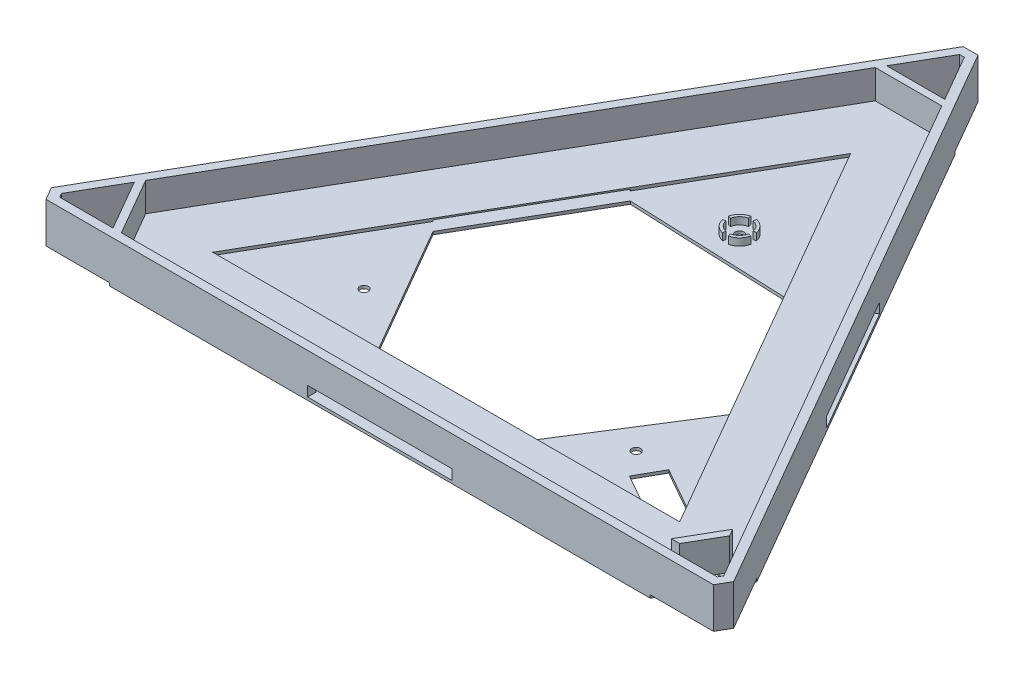
SolidWorks part; units mm, degrees
ref_plane "Front Plane" through (0, 0, 0) normal (0, 0, 1) x (1, 0, 0)
ref_plane "Top Plane" through (0, 0, 0) normal (0, 1, 0) x (1, 0, 0)
ref_plane "Right Plane" through (0, 0, 0) normal (1, 0, 0) x (0, 0, -1)
sketch "Sketch1" plane through (0, 0, 0) normal (0, 1, 0) x (1, 0, 0)
  line L0 (351.2729, 67.6655) -> (468.273, -134.9846)
  line L1 (347.2728, 67.6655) -> (347.2728, 65.1655) construction
  line L2 (409.773, -33.6595) -> (407.6079, -34.9095) construction
  line L3 (468.273, -134.9846) -> (464.2732, -141.9124)
  line L4 (230.2733, -141.9124) -> (464.2732, -141.9124)
  line L5 (230.2733, -141.9124) -> (226.2727, -134.9842)
  line L6 (226.2727, -134.9842) -> (343.2728, 67.6655)
  line L7 (353.4142, 63.9567) -> (351.2491, 62.7067) construction
  line L8 (347.2733, -141.9124) -> (347.2733, -139.4124) construction
  line L9 (231.7167, -139.4124) -> (462.8299, -139.4124)
  line L10 (284.7727, -33.6594) -> (286.9378, -34.9094) construction
  line L11 (344.7161, 65.1655) -> (349.8295, 65.1655)
  line L12 (465.3862, -134.9846) -> (349.8295, 65.1655)
  line L13 (466.2731, -138.4485) -> (464.1081, -137.1985) construction
  line L14 (462.8299, -139.4124) -> (465.3862, -134.9846)
  line L15 (229.1594, -134.9842) -> (344.7161, 65.1655)
  line L16 (229.1594, -134.9842) -> (231.7167, -139.4124)
  line L17 (286.9378, -34.9094) -> (287.3708, -35.1594) construction
  line L18 (230.438, -137.1983) -> (230.871, -136.9483) construction
  line L19 (232.0053, -138.9123) -> (229.7368, -134.9842)
  line L20 (343.2728, 67.6655) -> (351.2729, 67.6655)
  line L21 (345.0048, 64.6655) -> (229.7368, -134.9842)
  line L22 (349.5409, 64.6655) -> (345.0048, 64.6655)
  line L23 (249.0568, -126.4468) -> (246.8918, -127.697) construction
  line L24 (407.6079, -34.9095) -> (407.1749, -35.1595) construction
  line L26 (233.4463, -136.4089) -> (251.9226, -136.4093)
  line L27 (464.8089, -134.9846) -> (462.5412, -138.9123)
  line L28 (462.5412, -138.9123) -> (232.0053, -138.9123)
  line L29 (251.9226, -136.4093) -> (241.8609, -118.9847)
  line L30 (241.8609, -118.9847) -> (232.6236, -134.9842)
  line L31 (232.6236, -134.9842) -> (233.4463, -136.4089)
  line L33 (287.3708, -35.1594) -> (289.5359, -36.4094) construction
  line L34 (254.8093, -136.4089) -> (243.3042, -116.4848)
  line L35 (335.7675, 43.666) -> (243.3042, -116.4848)
  line L36 (358.7782, 43.666) -> (335.7675, 43.666)
  line L38 (289.5359, -36.4094) -> (306.8564, -46.4094) construction
  line L41 (461.939, -134.9846) -> (461.1164, -136.4093)
  line L42 (347.2688, -136.4172) -> (347.2688, -116.4172) construction
  line L43 (442.6021, -136.4093) -> (452.6999, -118.9847)
  line L44 (245.2636, -119.878) -> (249.0568, -126.4468) construction
  line L45 (452.6999, -118.9847) -> (461.939, -134.9846)
  line L48 (461.1164, -136.4093) -> (442.6021, -136.4093)
  line L49 (405.0134, -36.4027) -> (387.6936, -46.404) construction
  line L50 (306.8564, -46.4094) -> (466.2731, -138.4485) construction
  line L51 (357.3348, 46.166) -> (337.2109, 46.166)
  line L52 (337.2109, 46.166) -> (346.4484, 62.1659)
  line L53 (346.4484, 62.1659) -> (348.0966, 62.164)
  line L54 (348.0966, 62.164) -> (357.3348, 46.166)
  line L55 (228.273, -138.4483) -> (387.6936, -46.404) construction
  line L56 (347.2688, -116.4172) -> (347.2728, 43.666) construction
  line L57 (266.4391, -116.428) -> (428.1137, -116.4172)
  line L58 (347.2736, 23.6092) -> (428.1137, -116.4172)
  line L59 (266.4391, -116.428) -> (347.2736, 23.6092)
  line L60 (439.7283, -136.4254) -> (439.7283, -132.9254) construction
  line L61 (451.2487, -116.4715) -> (448.6507, -117.9717) construction
  line L62 (452.6999, -118.9847) -> (358.7782, 43.666)
  line L63 (442.6021, -136.4093) -> (254.8093, -136.4089)
  line L64 (441.749, -132.9254) -> (444.621, -132.9254)
  line L65 (448.6507, -117.9717) -> (450.9647, -121.979) construction
  line L66 (449.5167, -119.4714) -> (450.9647, -121.979)
  line L67 (441.749, -132.9254) -> (449.5167, -119.4714)
  line L68 (450.9647, -121.979) -> (444.621, -132.9254)
  point P13 (407.6079, -34.9095)
  point P20 (464.1081, -137.1985)
  point P23 (347.2733, -139.4124)
  point P25 (347.2732, -141.9124)
  point P27 (347.2728, 65.1655)
  point P31 (286.9378, -34.9094)
  point P37 (287.3708, -35.1594)
  point P39 (230.871, -136.9483)
  point P41 (347.2728, 64.6655)
  point P45 (407.1749, -35.1595)
  point P50 (246.8918, -127.697)
  point P56 (289.5359, -36.4094)
  point P58 (249.0568, -126.4468)
  point P60 (347.2728, 43.666)
  point P62 (345.0048, -136.4089)
  point P64 (445.4885, -126.4485)
  point P71 (447.651, -127.697)
  point P77 (347.2728, 46.166)
  point P84 (347.2688, -116.4172)
  point P87 (387.6936, -46.404)
  point P89 (306.8564, -46.4094)
  point P100 (405.0134, -36.4027)
  dimension "D1" = 2.5
  dimension "D2" = 2.5
  dimension "D3" = 2.5
  dimension "D4" = 2.5
  dimension "D5" = 2.5
  dimension "D6" = 2.5
  dimension "D7" = 0.5
  dimension "D8" = 0.5
  dimension "D9" = 0.5
  dimension "D10" = 2.5
  dimension "D11" = 2.5
  dimension "D12" = 20
  dimension "D13" = 20
  dimension "D14" = 20
  dimension "D15" = 3.5
  dimension "D16" = 3
extrude "Boss-Extrude1" add sketch "Sketch1" along normal blind 1 contours L36 L35 L34 L57 L59 L58 region at (251.4484, 0, 125.0658)
extrude "Boss-Extrude2" add sketch "Sketch1<9>" along normal blind 11 contours L28 L27 L22 L21 L19 L31 L30 L29 L26 L34 L35 L36 L41 L48 L43 L45 L53 L54 L51 L52 | L68 L64 L67 L66 region at (230.7087, 0, 137.042)
sketch "Sketch1<9>" plane through (0, 0, 0) normal (0, 1, 0) x (1, 0, 0) same geometry as "Sketch1"
extrude "Boss-Extrude3" add sketch "Sketch1<10>" along normal blind 5 and the other way blind 3 contours L28 L27 L22 L21 L19 L31 L30 L29 L26 L34 L35 L36 L41 L48 L43 L45 L53 L54 L51 L52 region at (230.7087, 0, 137.042)
sketch "Sketch1<10>" plane through (0, 0, 0) normal (0, 1, 0) x (1, 0, 0) same geometry as "Sketch1"
sketch "Sketch3" plane through (290.5896, 0, -167.772) normal (0.866, 0, -0.5) x (-0.5, 0, -0.866)
  line L1 (-261.593, -6.5) -> (-211.593, -6.5)
  line L2 (-261.593, -6.5) -> (-261.593, 0.5)
  line L3 (-261.593, 0.5) -> (-211.593, 0.5)
  line L4 (-211.593, -6.5) -> (-211.593, 0.5)
  line L5 (-261.593, -6.5) -> (-211.593, 0.5) construction
  line L6 (-261.593, 0.5) -> (-211.593, -6.5) construction
  point P0 (-236.593, -3)
  dimension "D1" = 50
  dimension "D2" = 7
extrude "Cut-Extrude3" cut sketch "Sketch3" against normal blind 25
sketch "Sketch5" plane through (0, 0, 139.4124) normal (0, 0, 1) x (1, 0, 0)
  line L0 (231.7167, -3) -> (462.8299, -3) construction
  line L1 (322.2733, -6.5) -> (372.2733, -6.5)
  line L2 (322.2733, -6.5) -> (322.2733, 0.5)
  line L3 (322.2733, 0.5) -> (372.2733, 0.5)
  line L4 (372.2733, -6.5) -> (372.2733, 0.5)
  line L5 (322.2733, -6.5) -> (372.2733, 0.5) construction
  line L6 (322.2733, 0.5) -> (372.2733, -6.5) construction
  point P0 (347.2733, -3)
  dimension "D1" = 50
  dimension "D2" = 7
extrude "Cut-Extrude4" cut sketch "Sketch5" against normal blind 25
sketch "Sketch6" plane through (230.3194, 0, 132.9752) normal (-0.866, 0, -0.5) x (-0.5, 0, 0.866)
  line L0 (2.3199, -3) -> (-228.7932, -3) construction
  line L1 (-138.2367, -6.5) -> (-88.2367, -6.5)
  line L2 (-138.2367, -6.5) -> (-138.2367, 0.5)
  line L3 (-138.2367, 0.5) -> (-88.2367, 0.5)
  line L4 (-88.2367, -6.5) -> (-88.2367, 0.5)
  line L5 (-138.2367, -6.5) -> (-88.2367, 0.5) construction
  line L6 (-138.2367, 0.5) -> (-88.2367, -6.5) construction
  point P0 (-113.2367, -3)
  dimension "D1" = 50
  dimension "D2" = 7
extrude "Cut-Extrude5" cut sketch "Sketch6" against normal blind 25
sketch "Sketch8" plane through (0, -3, 0) normal (0, -1, 0) x (1, 0, 0)
  line L0 (246.8918, 127.697) -> (257.9651, 146.8734) construction
  line L1 (251.9226, 136.4093) -> (241.8609, 118.9847) construction
  line L2 (447.651, 127.697) -> (454.4275, 116.0035) construction
  line L3 (442.6021, 136.4093) -> (452.6999, 118.9847) construction
  line L4 (465.3862, 134.9846) -> (421.3861, 58.7742) construction
  line L5 (347.2728, -46.166) -> (333.7468, -46.166) construction
  line L6 (357.3348, -46.166) -> (337.2109, -46.166) construction
  line L7 (299.4378, 13.2587) -> (344.7161, -65.1655) construction
  line L8 (246.8918, 127.697) -> (240.1287, 115.9849)
  line L9 (229.1594, 134.9842) -> (274.4378, 56.56) construction
  line L10 (240.1287, 115.9849) -> (333.7468, -46.166)
  line L11 (333.7468, -46.166) -> (360.7989, -46.166)
  line L12 (396.3861, 15.4729) -> (349.8295, -65.1655) construction
  line L13 (360.7989, -46.166) -> (454.4275, 116.0035)
  line L15 (372.2733, 139.4124) -> (462.8299, 139.4124) construction
  line L16 (440.9124, 139.4124) -> (253.6568, 139.4124)
  line L17 (231.7167, 139.4124) -> (322.2733, 139.4124) construction
  line L18 (253.6568, 139.4124) -> (246.8918, 127.697)
  line L19 (322.2733, 116.4243) -> (294.3582, 68.0611)
  line L20 (294.3582, 68.0611) -> (319.3545, 24.7577)
  line L21 (319.3545, 24.7577) -> (376.4737, 26.9694)
  line L22 (376.4737, 26.9694) -> (401.4727, 70.2712)
  line L23 (401.4727, 70.2712) -> (372.2733, 116.4209)
  line L24 (372.2733, 116.4209) -> (322.2733, 116.4243)
  line L25 (386.873, 93.3461) -> (395.3235, 98.6928) construction
  line L30 (308.3157, 92.2427) -> (299.6549, 97.2417) construction
  line L31 (347.9141, 25.8635) -> (348.3013, 15.8635) construction
  line L32 (440.9124, 139.4124) -> (445.2267, 131.9864)
  line L33 (454.4275, 116.0035) -> (450.147, 123.2807)
  line L34 (401.698, 107.3846) -> (445.2267, 131.9864)
  line L35 (450.147, 123.2807) -> (406.6183, 98.6788)
  line L36 (401.698, 107.3846) -> (406.6183, 98.6788)
  circle A0 centre (395.3235, 98.6928) radius 1.5
  circle A1 centre (348.3013, 15.8635) radius 1.5
  circle A2 centre (299.6549, 97.2417) radius 1.5
  dimension "D6" = 3
  dimension "D7" = 3
  dimension "D8" = 3
  dimension "D1" = 10
  dimension "D2" = 50
  dimension "D3" = 10
  dimension "D4" = 10
  dimension "D5" = 10
extrude "Boss-Extrude5" add sketch "Sketch8" along normal blind 1
sketch "Sketch12" plane through (0, -3, 0) normal (0, 1, 0) x (1, 0, 0)
  line L0 (348.3013, -11.8635) -> (348.3013, -10.8635) construction
  line L1 (348.3013, -10.8635) -> (349.2963, -10.9635) construction
  line L2 (349.2963, -10.9635) -> (349.0973, -11.9435)
  line L3 (348.3013, -10.8635) -> (347.3063, -10.9635) construction
  line L4 (347.3063, -10.9635) -> (347.5053, -11.9435)
  line L5 (352.3013, -15.8635) -> (353.3013, -15.8635) construction
  line L6 (344.3013, -15.8635) -> (343.3013, -15.8635) construction
  line L7 (348.3013, -19.8635) -> (348.3013, -20.8635) construction
  line L8 (353.3013, -15.8635) -> (353.2013, -14.8685) construction
  line L9 (353.3013, -15.8635) -> (353.2013, -16.8585) construction
  line L10 (343.3013, -15.8635) -> (343.4013, -14.8685) construction
  line L11 (343.3013, -15.8635) -> (343.4013, -16.8585) construction
  line L12 (348.3013, -20.8635) -> (349.2963, -20.7635) construction
  line L13 (348.3013, -20.8635) -> (347.3063, -20.7635) construction
  line L14 (343.4013, -14.8685) -> (348.3013, -15.8635) construction
  line L15 (348.3013, -15.8635) -> (353.2013, -14.8685) construction
  line L16 (343.4013, -16.8585) -> (348.3013, -15.8635) construction
  line L17 (348.3013, -15.8635) -> (353.2013, -16.8585) construction
  line L18 (347.3063, -20.7635) -> (348.3013, -15.8635) construction
  line L19 (348.3013, -15.8635) -> (349.2963, -20.7635) construction
  line L20 (343.4013, -14.8685) -> (344.3813, -15.0675)
  line L21 (343.4013, -16.8585) -> (344.3813, -16.6595)
  line L22 (347.3063, -20.7635) -> (347.5053, -19.7835)
  line L23 (349.2963, -20.7635) -> (349.0973, -19.7835)
  line L24 (353.2013, -14.8685) -> (352.2213, -15.0675)
  line L25 (353.2013, -16.8585) -> (352.2213, -16.6595)
  circle A0 centre (348.3013, -15.8635) radius 5
  circle A1 centre (395.3235, -98.6928) radius 5
  circle A2 centre (299.6549, -97.2417) radius 5
  circle A3 centre (348.3013, -15.8635) radius 4
  circle A4 centre (395.3235, -98.6928) radius 4
  circle A5 centre (299.6549, -97.2417) radius 4
  dimension "D1" = 10
  dimension "D2" = 10
  dimension "D3" = 10
  dimension "D4" = 8
  dimension "D5" = 8
  dimension "D6" = 8
  dimension "D7" = 1
  dimension "D8" = 1
  dimension "D9" = 1
  dimension "D10" = 1
  dimension "D11" = 1
  dimension "D12" = 1
  dimension "D13" = 1
  dimension "D14" = 1
extrude "Boss-Extrude7" add sketch "Sketch12" along normal blind 2.5 contours A3 L4 A0 L20 | A3 L24 A0 L2 | A3 L23 A0 L25 | A3 L21 A0 L22 region at (351.3172, -3, 12.8476) region at (345.2854, -3, 12.8476) region at (351.3172, -3, 18.8794) region at (345.2854, -3, 18.8794)
